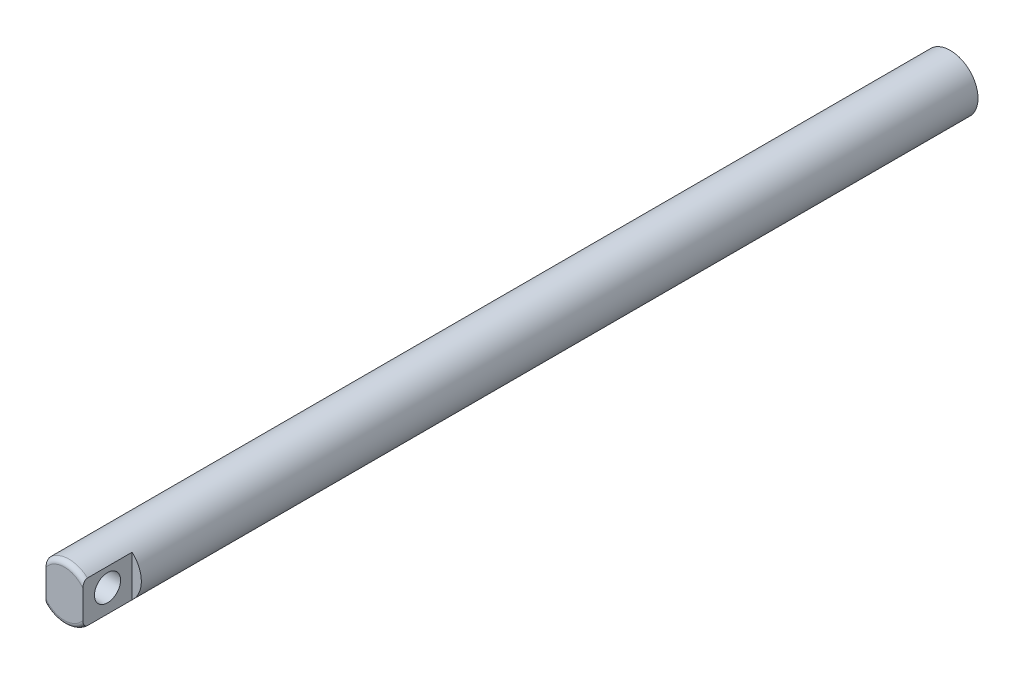
SolidWorks part; units mm, degrees
material "AISI 316 Stainless Steel Sheet (SS)"
ref_plane "Front Plane" through (0, 0, 0) normal (0, 0, 1) x (1, 0, 0)
ref_plane "Top Plane" through (0, 0, 0) normal (0, 1, 0) x (1, 0, 0)
ref_plane "Right Plane" through (0, 0, 0) normal (1, 0, 0) x (0, 0, -1)
sketch "Sketch1" plane through (0, 0, 0) normal (0, 0, 1) x (1, 0, 0)
  circle A0 centre (0, 0) radius 4.5
extrude "Boss-Extrude1" add sketch "Sketch1" along normal blind 144
sketch "Sketch3" plane through (0, 0, 0) normal (1, 0, 0) x (0, 0, -1)
  line L0 (-144, 4.5) -> (-144, -4.5) construction
  line L1 (-144, 4.5) -> (-144, -4.5)
  line L2 (-136, 4.5) -> (-136, -4.5)
  line L4 (-136, 4.5) -> (-144, 4.5)
  line L5 (-144, -4.5) -> (-136, -4.5)
  dimension "D1" = 8
  dimension "D2" = 9
extrude "Cut-Extrude1" cut sketch "Sketch3" against normal blind 1.5 from offset 3 offset against normal yes
mirror "Mirror1" about plane through (0, 0, 0) normal (1, 0, 0) of "Cut-Extrude1"
fillet "Fillet1" radius 0.75 2 edges at (0, -4.5, 144) (0, 4.5, 144)
sketch "Sketch4" plane through (3, 0, 0) normal (1, 0, 0) x (0, 0, -1)
  line L0 (-144, 2.25) -> (-144, -2.25) construction
  line L1 (-143.25, 3.3541) -> (-136, 3.3541) construction
  circle A0 centre (-140, 0.3541) radius 2.125
  dimension "D1" = 4
  dimension "D2" = 3
extrude "Cut-Extrude2" cut sketch "Sketch4" against normal through all both and the other way through all
